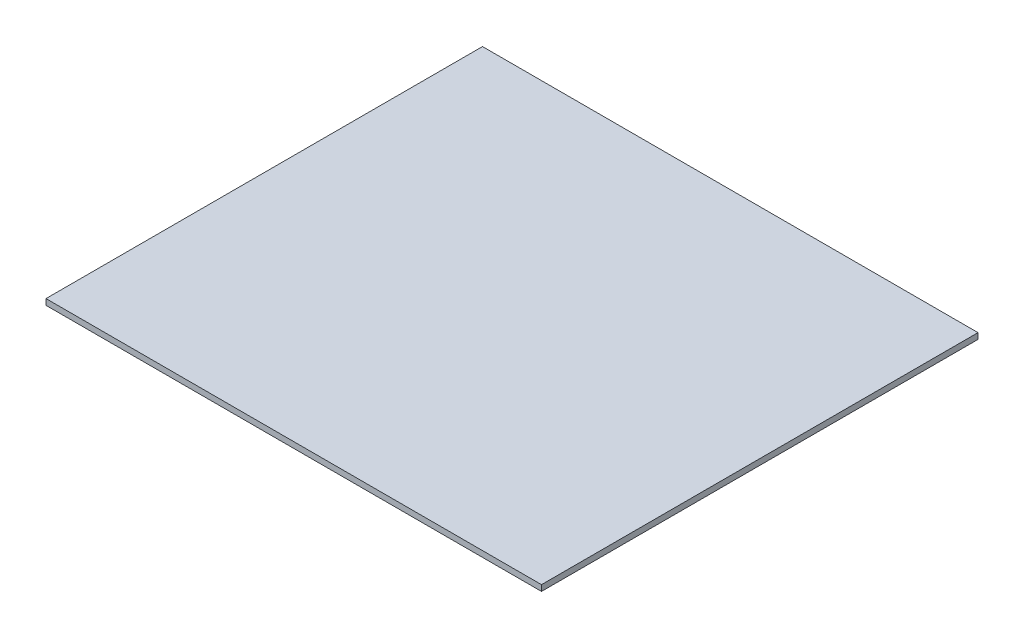
SolidWorks part; units mm, degrees
ref_plane "Front Plane" through (0, 0, 0) normal (0, 0, 1) x (1, 0, 0)
ref_plane "Top Plane" through (0, 0, 0) normal (0, 1, 0) x (1, 0, 0)
ref_plane "Right Plane" through (0, 0, 0) normal (1, 0, 0) x (0, 0, -1)
sketch "Sketch1" plane through (0, 0, 0) normal (0, 1, 0) x (1, 0, 0)
  line L1 (-133.35, -117.475) -> (133.35, -117.475)
  line L2 (-133.35, -117.475) -> (-133.35, 117.475)
  line L3 (-133.35, 117.475) -> (133.35, 117.475)
  line L4 (133.35, -117.475) -> (133.35, 117.475)
  line L5 (-133.35, -117.475) -> (133.35, 117.475) construction
  line L6 (-133.35, 117.475) -> (133.35, -117.475) construction
  point P0 (0, 0)
  dimension "D1" = 234.95
  dimension "D2" = 266.7
extrude "Boss-Extrude1" add sketch "Sketch1" along normal mid plane 3.175 contours L2 L3 L4 L1
